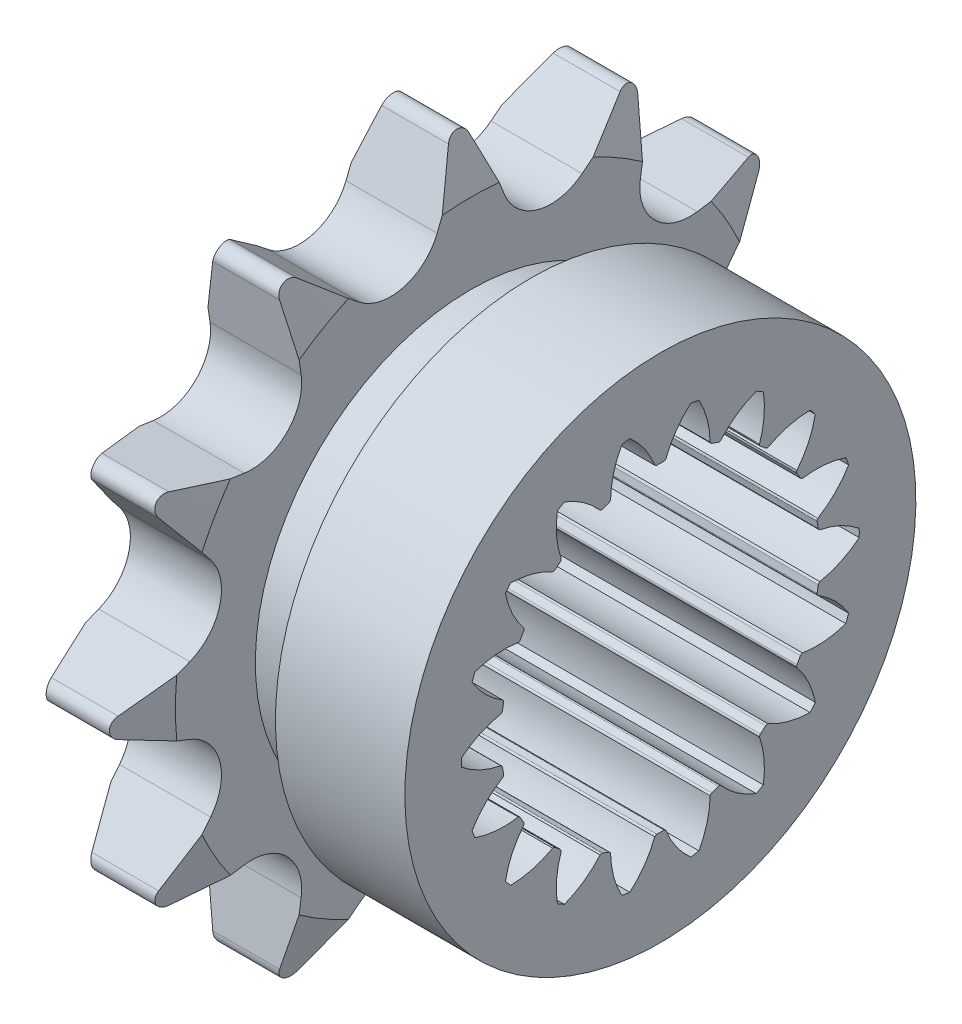
SolidWorks part; units mm, degrees
material "1144"
ref_plane "Front Plane" through (0, 0, 0) normal (0, 0, 1) x (1, 0, 0)
ref_plane "Top Plane" through (0, 0, 0) normal (0, 1, 0) x (1, 0, 0)
ref_plane "Right Plane" through (0, 0, 0) normal (1, 0, 0) x (0, 0, -1)
ref_axis "Axis1" through (-63.0158, 0, 0) along (1, 0, 0)
sketch "Sketch1" plane through (0, 0, 0) normal (0, 0, 1) x (1, 0, 0)
  line L0 (3.6068, 17.0561) -> (3.6068, 0) construction
  line L1 (22.225, 0) -> (22.225, 20.2311)
  line L3 (7.2136, 17.0561) -> (0, 17.0561)
  line L7 (0, 27.5082) -> (0, 30.0482) construction
  line L8 (0, 27.5082) -> (7.2136, 27.5082)
  line L9 (22.225, 0) -> (0, 0)
  line L10 (0, 0) -> (-84.1773, 0) construction
  line L11 (0, 17.0561) -> (0, 27.5082) construction
  line L12 (7.2136, 27.5082) -> (73.2462, 27.5082) construction
  line L13 (22.225, 0) -> (22.225, -20.2311) construction
  line L14 (3.6068, 0) -> (3.6068, -17.0561)
  line L15 (-15.4432, -17.0561) -> (22.6568, -17.0561)
  point P11 (0, 30.0482)
  dimension "D1" = 2.54
  dimension "hub_dia" = 40.4622
  dimension "width_teetth" = 7.2136
  dimension "D2" = 38.1
  dimension "length_thru" = 22.225
  dimension "OD" = 55.0164
  dimension "length_over_teeth" = 7.2136
  dimension "recess_hub_diam" = 34.1122
  dimension "hub_type" = 22.225
  dimension "projection 1" = 15.0114
  dimension "projection 2" = 0
sketch "Sketch2" plane through (0, 0, 0) normal (1, 0, 0) x (0, 0, -1)
  line L0 (0, 0) -> (0, 27.5082) construction
  line L1 (0, 0) -> (-13.7541, 23.8228) construction
  line L2 (0, 0) -> (-6.3502, 23.6991) construction
  line L3 (-0.8057, 26.9597) -> (-2.6638, 22.246)
  line L4 (-2.6638, 22.246) -> (-6.3502, 23.6991) construction
  line L5 (-0.8217, 27.4959) -> (0, 0) construction
  line L6 (-2.735, 27.3719) -> (0, 0) construction
  line L7 (-6.3502, 23.6991) -> (-2.4074, 24.0931) construction
  arc A1 (0, 27.5082) -> (-13.7541, 23.8228) centre (0, 0) ccw
  circle A2 centre (0, 0) radius 24.5351 construction
  circle A3 centre (-6.3502, 23.6991) radius 3.9624
  arc A4 (0, 27.5082) -> (-0.8057, 26.9597) centre (0, 26.6421) ccw
  dimension "pitch_diam" = 49.0703
  dimension "roller_diam" = 7.9248
  dimension "D1" = 1.712
  dimension "ang_1" = 30
  dimension "OD/2" = 27.5082
sketch "Taper Per Foot" plane through (0, 0, 0) normal (0, 0, 1) x (1, 0, 0)
  line L0 (22.225, 0) -> (22.225, 127)
  line L1 (22.225, 0) -> (22.225, 20.2311) construction
  line L2 (22.225, 127) -> (-282.575, 6.35)
  line L3 (-282.575, 6.35) -> (-282.575, 0)
  line L4 (-282.575, 0) -> (22.225, 0)
  line L5 (-282.575, 0) -> (-285.7823, 0) construction
  line L6 (-282.575, 6.35) -> (22.225, 6.35)
  line L7 (22.225, 6.35) -> (22.225, 127)
  dimension "1 Ft" = 304.8
  dimension "1 in" = 254
  dimension "Small End Diam" = 12.7
  dimension "Large End Diam" = 12.7
ref_plane "Plane1" through (7.2136, 0, 0) normal (1, 0, 0) x (0, 0, -1)
ref_plane "Plane2" through (7.2136, 0, 0) normal (1, 0, 0) x (0, 0, -1)
ref_plane "Plane3" through (0, 17.0561, 0) normal (-1, 0, 0) x (0, 0, 1)
ref_plane "Plane4" through (22.225, 0, 0) normal (1, 0, 0) x (0, 0, -1)
ref_plane "Plane5" through (3.6068, 0, 0) normal (1, 0, 0) x (0, 0, -1)
sketch "Sketch13" plane through (0, 0, 0) normal (0, 0, 1) x (1, 0, 0)
  line L0 (22.225, 0) -> (22.225, 20.2311) construction
  line L1 (0, 0) -> (22.225, 0)
  line L2 (0, 0) -> (0, 27.5082)
  line L3 (0, 27.5082) -> (22.225, 27.5082)
  line L4 (22.225, 0) -> (22.225, 27.5082)
revolve "Revolve1" add sketch "Sketch13" angle 360 about L10
sketch "Sketch6" plane through (0, -16.51, 0) normal (1, 0, 0) x (0, 0, -1)
  line L0 (-0.8057, 43.4697) -> (-2.6638, 38.756) construction
  line L1 (-0.8057, 43.4697) -> (-2.6638, 38.756)
  line L2 (-6.3502, 40.2091) -> (0, 16.51) construction
  line L3 (-12.7821, 40.2607) -> (-8.8161, 37.1075)
  arc A0 (0, 44.0182) -> (-0.8057, 43.4697) centre (0, 43.1521) ccw construction
  arc A1 (0, 44.0182) -> (-0.8057, 43.4697) centre (0, 43.1521) ccw
  arc A2 (-13.7541, 40.3328) -> (-12.7821, 40.2607) centre (-13.3211, 39.5828) cw
  arc A3 (-2.6638, 38.756) -> (-8.8161, 37.1075) centre (-6.3502, 40.2091) cw
  arc A4 (0, 44.0182) -> (-13.7541, 40.3328) centre (0, 16.51) ccw
extrude "Cut-Extrude1" cut sketch "Sketch6" along normal up to vertex (7.2136 mm away) up to point (7.2136, 17.0561, 0)
pattern_circular "CirPattern1" count 12 over 360 about axis through (-63.0158, 0, 0) along (1, 0, 0) of "Cut-Extrude1"
sketch "Sketch15" plane through (0, 0, 0) normal (0, 0, 1) x (1, 0, 0)
  line L1 (134.2136, 20.2311) -> (7.2136, 20.2311)
  line L2 (134.2136, 20.2311) -> (134.2136, 42.7482)
  line L3 (134.2136, 42.7482) -> (7.2136, 42.7482)
  line L4 (7.2136, 20.2311) -> (7.2136, 42.7482)
  line L5 (3.6068, 216.4797) -> (3.6068, 17.0561) construction
  line L6 (-127, 20.2311) -> (0, 20.2311)
  line L7 (0, 20.2311) -> (0, 42.7482)
  line L8 (-127, 42.7482) -> (0, 42.7482)
  line L9 (-127, 20.2311) -> (-127, 42.7482)
  dimension "D1" = 12.7
  dimension "D2" = 127
revolve "hub Cut-Revolve3" cut sketch "Sketch15" angle 360 about L10
sketch "Sketch4" plane through (0, 0, 0) normal (0, 0, 1) x (1, 0, 0)
  line L0 (0, 27.5082) -> (1.1045, 27.5082)
  line L2 (1.1045, 27.5082) -> (0, 23.3861)
  line L4 (0, 23.3861) -> (0, 27.5082)
  line L5 (3.6068, 27.5082) -> (3.6068, 44.9612) construction
  line L6 (7.2136, 27.5082) -> (6.1091, 27.5082)
  line L7 (7.2136, 23.3861) -> (7.2136, 27.5082)
  line L8 (6.1091, 27.5082) -> (7.2136, 23.3861)
  line L9 (0, 0) -> (-52.1231, 0) construction
  line L10 (0, 0) -> (-84.1773, 0) construction
  line L17 (0, 27.5082) -> (7.2136, 27.5082) construction
  dimension "D1" = 15
  dimension "D2" = 4.1221
revolve "Teeth Chamfer" cut sketch "Sketch4" angle 360 about L9
sketch "Sketch16" plane through (0, 0, 0) normal (0, 0, 1) x (1, 0, 0)
  line L1 (7.2136, 20.2311) -> (11.9761, 20.2311)
  line L2 (7.2136, 20.2311) -> (7.2136, 17.0561)
  line L3 (7.2136, 17.0561) -> (11.9761, 17.0561)
  line L4 (11.9761, 20.2311) -> (11.9761, 17.0561)
  line L5 (11.9761, 20.2311) -> (22.225, 20.2311) construction
  dimension "recess_width" = 4.7625
  dimension "recess_height" = 3.175
revolve "Recess" cut sketch "Sketch16" angle 360 about L10
sketch "Sketch32" plane through (22.225, 0, 0) normal (1, 0, 0) x (0, 0, -1)
  circle A1 centre (0, 0) radius 20.2311
  circle A2 centre (0, 0) radius 20.2311
  dimension "D1" = 0
extrude "Collar Reduction" [suppressed] cut sketch "Sketch32" against normal offset from surface (2.455 mm away) 19.77 up to face at (0, 0, 0)
ref_plane "Sprocket Teeth Center" through (3.6068, 0, 0) normal (-1, 0, 0) x (0, 0, 1)
sketch "Sketch35" plane through (3.6068, 0, 0) normal (1, 0, 0) x (0, 0, -1)
  circle A0 centre (0, 0) radius 24.5351 construction
  circle A1 centre (0, 0) radius 24.5351 construction
sketch "Sketch36" plane through (0, 0, 0) normal (-1, 0, 0) x (0, 0, 1)
  arc A34 (-7.5926, 13.7968) -> (-4.773, 11.8201) centre (-10.1337, 7.1728) cw
  arc A35 (-4.773, 11.8201) -> (-4.5847, 11.7902) centre (-4.6432, 12.0297) ccw
  arc A36 (-0.6644, 3.068) -> (-0.7894, 2.924) centre (-0.8986, 3.1451) cw
  arc A37 (-4.5847, 11.7902) -> (-4.0582, 11.9816) centre (0, 0) cw
  arc A38 (-8.1521, 13.4738) -> (-7.5639, 13.8125) centre (0, 0) cw
  arc A39 (-8.3407, 9.5111) -> (-7.9114, 9.8711) centre (0, 0) cw
  arc A40 (-7.85, 10.0436) -> (-7.9183, 9.8655) centre (-8.0965, 10.0359) cw
  arc A41 (-8.1521, 13.4738) -> (-7.85, 10.0436) centre (-1.145, 12.3625) ccw
  arc A42 (-2.4159, 15.5616) -> (-0.4424, 12.7398) centre (-7.0693, 10.2062) cw
  arc A43 (-0.4424, 12.7398) -> (-0.2757, 12.6472) centre (-0.2487, 12.8923) ccw
  arc A44 (-0.2757, 12.6472) -> (0.2845, 12.647) centre (0, 0) cw
  arc A45 (-3.0522, 15.4494) -> (-2.3836, 15.5666) centre (0, 0) cw
  arc A46 (-4.5847, 11.7902) -> (-4.0582, 11.9816) centre (0, 0) cw
  arc A47 (-3.9415, 12.1228) -> (-4.0666, 11.9788) centre (-4.1757, 12.1999) cw
  arc A48 (-3.0522, 15.4494) -> (-3.9415, 12.1228) centre (3.1523, 12.0085) ccw
  arc A49 (3.0522, 15.4494) -> (3.9415, 12.1228) centre (-3.1523, 12.0085) cw
  arc A50 (3.9415, 12.1228) -> (4.0666, 11.9788) centre (4.1757, 12.1999) ccw
  arc A51 (4.0666, 11.9788) -> (4.5929, 11.787) centre (0, 0) cw
  arc A52 (2.4159, 15.5616) -> (3.0842, 15.443) centre (0, 0) cw
  arc A53 (-0.2757, 12.6472) -> (0.2845, 12.647) centre (0, 0) cw
  arc A54 (0.4424, 12.7398) -> (0.2757, 12.6472) centre (0.2487, 12.8923) cw
  arc A55 (2.4159, 15.5616) -> (0.4424, 12.7398) centre (7.0693, 10.2062) ccw
  arc A56 (8.1521, 13.4738) -> (7.85, 10.0436) centre (1.145, 12.3625) cw
  arc A57 (7.85, 10.0436) -> (7.9183, 9.8655) centre (8.0965, 10.0359) ccw
  arc A58 (7.9183, 9.8655) -> (8.3473, 9.5053) centre (0, 0) cw
  arc A59 (7.5926, 13.7968) -> (8.18, 13.4568) centre (0, 0) cw
  arc A60 (4.0666, 11.9788) -> (4.5929, 11.787) centre (0, 0) cw
  arc A61 (4.773, 11.8201) -> (4.5847, 11.7902) centre (4.6432, 12.0297) cw
  arc A62 (7.5926, 13.7968) -> (4.773, 11.8201) centre (10.1337, 7.1728) ccw
  arc A63 (12.2688, 9.873) -> (10.8117, 6.753) centre (5.3042, 11.2253) cw
  arc A64 (10.8117, 6.753) -> (10.815, 6.5624) centre (11.0407, 6.6616) ccw
  arc A65 (10.815, 6.5624) -> (11.0949, 6.0771) centre (0, 0) cw
  arc A66 (11.8535, 10.368) -> (12.2892, 9.8476) centre (0, 0) cw
  arc A67 (7.9183, 9.8655) -> (8.3473, 9.5053) centre (0, 0) cw
  arc A68 (8.5279, 9.4748) -> (8.3407, 9.5111) centre (8.4775, 9.7162) cw
  arc A69 (11.8535, 10.368) -> (8.5279, 9.4748) centre (11.9758, 3.2743) ccw
  arc A70 (14.9057, 5.0814) -> (12.4694, 2.6479) centre (8.8236, 8.7342) cw
  arc A71 (12.4694, 2.6479) -> (12.4072, 2.4677) centre (12.6532, 2.4837) ccw
  arc A72 (12.4072, 2.4677) -> (12.5043, 1.916) centre (0, 0) cw
  arc A73 (14.6847, 5.6886) -> (14.9162, 5.0505) centre (0, 0) cw
  arc A74 (10.815, 6.5624) -> (11.0949, 6.0771) centre (0, 0) cw
  arc A75 (11.2542, 5.9867) -> (11.0907, 6.0849) centre (11.2894, 6.2307) cw
  arc A76 (14.6847, 5.6886) -> (11.2542, 5.9867) centre (12.3735, -1.0191) ccw
  arc A77 (15.7447, -0.3231) -> (12.623, -1.7765) centre (11.2787, 5.1896) cw
  arc A78 (12.623, -1.7765) -> (12.503, -1.9247) centre (12.7396, -1.9938) ccw
  arc A79 (12.503, -1.9247) -> (12.4055, -2.4763) centre (0, 0) cw
  arc A80 (15.7447, 0.3231) -> (15.744, -0.3557) centre (0, 0) cw
  arc A81 (12.4072, 2.4677) -> (12.5043, 1.916) centre (0, 0) cw
  arc A82 (12.623, 1.7765) -> (12.503, 1.9247) centre (12.7396, 1.9938) cw
  arc A83 (15.7447, 0.3231) -> (12.623, 1.7765) centre (11.2787, -5.1896) ccw
  arc A84 (14.6847, -5.6886) -> (11.2542, -5.9867) centre (12.3735, 1.0191) cw
  arc A85 (11.2542, -5.9867) -> (11.0907, -6.0849) centre (11.2894, -6.2307) ccw
  arc A86 (11.0907, -6.0849) -> (10.8104, -6.5699) centre (0, 0) cw
  arc A87 (14.9057, -5.0814) -> (14.6728, -5.719) centre (0, 0) cw
  arc A88 (12.503, -1.9247) -> (12.4055, -2.4763) centre (0, 0) cw
  arc A89 (12.4694, -2.6479) -> (12.4072, -2.4677) centre (12.6532, -2.4837) cw
  arc A90 (14.9057, -5.0814) -> (12.4694, -2.6479) centre (8.8236, -8.7342) ccw
  arc A91 (11.8535, -10.368) -> (8.5279, -9.4748) centre (11.9758, -3.2743) cw
  arc A92 (8.5279, -9.4748) -> (8.3407, -9.5111) centre (8.4775, -9.7162) ccw
  arc A93 (8.3407, -9.5111) -> (7.9114, -9.8711) centre (0, 0) cw
  arc A94 (12.2688, -9.873) -> (11.832, -10.3925) centre (0, 0) cw
  arc A95 (11.0907, -6.0849) -> (10.8104, -6.5699) centre (0, 0) cw
  arc A96 (10.8117, -6.753) -> (10.815, -6.5624) centre (11.0407, -6.6616) cw
  arc A97 (12.2688, -9.873) -> (10.8117, -6.753) centre (5.3042, -11.2253) ccw
  arc A98 (7.5926, -13.7968) -> (4.773, -11.8201) centre (10.1337, -7.1728) cw
  arc A99 (4.773, -11.8201) -> (4.5847, -11.7902) centre (4.6432, -12.0297) ccw
  arc A100 (4.5847, -11.7902) -> (4.0582, -11.9816) centre (0, 0) cw
  arc A101 (8.1521, -13.4738) -> (7.5639, -13.8125) centre (0, 0) cw
  arc A102 (8.3407, -9.5111) -> (7.9114, -9.8711) centre (0, 0) cw
  arc A103 (7.85, -10.0436) -> (7.9183, -9.8655) centre (8.0965, -10.0359) cw
  arc A104 (8.1521, -13.4738) -> (7.85, -10.0436) centre (1.145, -12.3625) ccw
  arc A105 (2.4159, -15.5616) -> (0.4424, -12.7398) centre (7.0693, -10.2062) cw
  arc A106 (0.4424, -12.7398) -> (0.2757, -12.6472) centre (0.2487, -12.8923) ccw
  arc A107 (0.2757, -12.6472) -> (-0.2845, -12.647) centre (0, 0) cw
  arc A108 (3.0522, -15.4494) -> (2.3836, -15.5666) centre (0, 0) cw
  arc A109 (4.5847, -11.7902) -> (4.0582, -11.9816) centre (0, 0) cw
  arc A110 (3.9415, -12.1228) -> (4.0666, -11.9788) centre (4.1757, -12.1999) cw
  arc A111 (3.0522, -15.4494) -> (3.9415, -12.1228) centre (-3.1523, -12.0085) ccw
  arc A112 (-3.0522, -15.4494) -> (-3.9415, -12.1228) centre (3.1523, -12.0085) cw
  arc A113 (-3.9415, -12.1228) -> (-4.0666, -11.9788) centre (-4.1757, -12.1999) ccw
  arc A114 (-4.0666, -11.9788) -> (-4.5929, -11.787) centre (0, 0) cw
  arc A115 (-2.4159, -15.5616) -> (-3.0842, -15.443) centre (0, 0) cw
  arc A116 (0.2757, -12.6472) -> (-0.2845, -12.647) centre (0, 0) cw
  arc A117 (-0.4424, -12.7398) -> (-0.2757, -12.6472) centre (-0.2487, -12.8923) cw
  arc A118 (-2.4159, -15.5616) -> (-0.4424, -12.7398) centre (-7.0693, -10.2062) ccw
  arc A119 (-8.1521, -13.4738) -> (-7.85, -10.0436) centre (-1.145, -12.3625) cw
  arc A120 (-7.85, -10.0436) -> (-7.9183, -9.8655) centre (-8.0965, -10.0359) ccw
  arc A121 (-7.9183, -9.8655) -> (-8.3473, -9.5053) centre (0, 0) cw
  arc A122 (-7.5926, -13.7968) -> (-8.18, -13.4568) centre (0, 0) cw
  arc A123 (-4.0666, -11.9788) -> (-4.5929, -11.787) centre (0, 0) cw
  arc A124 (-4.773, -11.8201) -> (-4.5847, -11.7902) centre (-4.6432, -12.0297) cw
  arc A125 (-7.5926, -13.7968) -> (-4.773, -11.8201) centre (-10.1337, -7.1728) ccw
  arc A126 (-12.2688, -9.873) -> (-10.8117, -6.753) centre (-5.3042, -11.2253) cw
  arc A127 (-10.8117, -6.753) -> (-10.815, -6.5624) centre (-11.0407, -6.6616) ccw
  arc A128 (-10.815, -6.5624) -> (-11.0949, -6.0771) centre (0, 0) cw
  arc A129 (-11.8535, -10.368) -> (-12.2892, -9.8476) centre (0, 0) cw
  arc A130 (-7.9183, -9.8655) -> (-8.3473, -9.5053) centre (0, 0) cw
  arc A131 (-8.5279, -9.4748) -> (-8.3407, -9.5111) centre (-8.4775, -9.7162) cw
  arc A132 (-11.8535, -10.368) -> (-8.5279, -9.4748) centre (-11.9758, -3.2743) ccw
  arc A133 (-14.9057, -5.0814) -> (-12.4694, -2.6479) centre (-8.8236, -8.7342) cw
  arc A134 (-12.4694, -2.6479) -> (-12.4072, -2.4677) centre (-12.6532, -2.4837) ccw
  arc A135 (-12.4072, -2.4677) -> (-12.5043, -1.916) centre (0, 0) cw
  arc A136 (-14.6847, -5.6886) -> (-14.9162, -5.0505) centre (0, 0) cw
  arc A137 (-10.815, -6.5624) -> (-11.0949, -6.0771) centre (0, 0) cw
  arc A138 (-11.2542, -5.9867) -> (-11.0907, -6.0849) centre (-11.2894, -6.2307) cw
  arc A139 (-14.6847, -5.6886) -> (-11.2542, -5.9867) centre (-12.3735, 1.0191) ccw
  arc A140 (-15.7447, 0.3231) -> (-12.623, 1.7765) centre (-11.2787, -5.1896) cw
  arc A141 (-12.623, 1.7765) -> (-12.503, 1.9247) centre (-12.7396, 1.9938) ccw
  arc A142 (-12.503, 1.9247) -> (-12.4055, 2.4763) centre (0, 0) cw
  arc A143 (-15.7447, -0.3231) -> (-15.744, 0.3557) centre (0, 0) cw
  arc A144 (-12.4072, -2.4677) -> (-12.5043, -1.916) centre (0, 0) cw
  arc A145 (-12.623, -1.7765) -> (-12.503, -1.9247) centre (-12.7396, -1.9938) cw
  arc A146 (-15.7447, -0.3231) -> (-12.623, -1.7765) centre (-11.2787, 5.1896) ccw
  arc A147 (-14.6847, 5.6886) -> (-11.2542, 5.9867) centre (-12.3735, -1.0191) cw
  arc A148 (-11.2542, 5.9867) -> (-11.0907, 6.0849) centre (-11.2894, 6.2307) ccw
  arc A149 (-11.0907, 6.0849) -> (-10.8104, 6.5699) centre (0, 0) cw
  arc A150 (-14.9057, 5.0814) -> (-14.6728, 5.719) centre (0, 0) cw
  arc A151 (-12.503, 1.9247) -> (-12.4055, 2.4763) centre (0, 0) cw
  arc A152 (-12.4694, 2.6479) -> (-12.4072, 2.4677) centre (-12.6532, 2.4837) cw
  arc A153 (-14.9057, 5.0814) -> (-12.4694, 2.6479) centre (-8.8236, 8.7342) ccw
  arc A154 (-11.8535, 10.368) -> (-8.5279, 9.4748) centre (-11.9758, 3.2743) cw
  arc A155 (-8.5279, 9.4748) -> (-8.3407, 9.5111) centre (-8.4775, 9.7162) ccw
  arc A156 (-8.3407, 9.5111) -> (-7.9114, 9.8711) centre (0, 0) cw
  arc A157 (-12.2688, 9.873) -> (-11.832, 10.3925) centre (0, 0) cw
  arc A158 (-11.0907, 6.0849) -> (-10.8104, 6.5699) centre (0, 0) cw
  arc A159 (-10.8117, 6.753) -> (-10.815, 6.5624) centre (-11.0407, 6.6616) cw
  arc A160 (-12.2688, 9.873) -> (-10.8117, 6.753) centre (-5.3042, 11.2253) ccw
  point P6 (-8.1521, 13.4738)
  point P24 (-3.1758, 15.7377)
  point P38 (2.2923, 15.8499)
  point P52 (7.469, 14.0851)
  point P66 (11.7299, 10.6563)
  point P81 (14.5611, 5.9769)
  point P95 (15.6211, 0.6114)
  point P109 (14.7821, -4.7931)
  point P123 (12.1452, -9.5847)
  point P137 (8.0286, -13.1855)
  point P151 (2.9286, -15.1611)
  point P165 (-2.5394, -15.2733)
  point P179 (-7.7161, -13.5085)
  point P193 (-11.977, -10.0797)
  point P207 (-14.8082, -5.4003)
  point P221 (-15.8682, -0.0348)
  point P235 (-15.0292, 5.3697)
  point P248 (-12.3924, 10.1613)
  point P258 (-0.1236, 0.2883)
extrude "Cut-Extrude2" cut sketch "Sketch36" against normal through all contours A157 A160 A159 A149 A148 A147 A150 A153 A152 A142 A141 A140 A143 A146 A145 A135 A134 A133 A136 A139 A138 A128 A127 A126 A129 A132 A131 A121 A120 A119 A122 A125 A124 A114 A113 A112 region at (0, 0, 0)
ref_axis "Axis2" through (22.225, 0, 0) along (-1, 0, 0)
